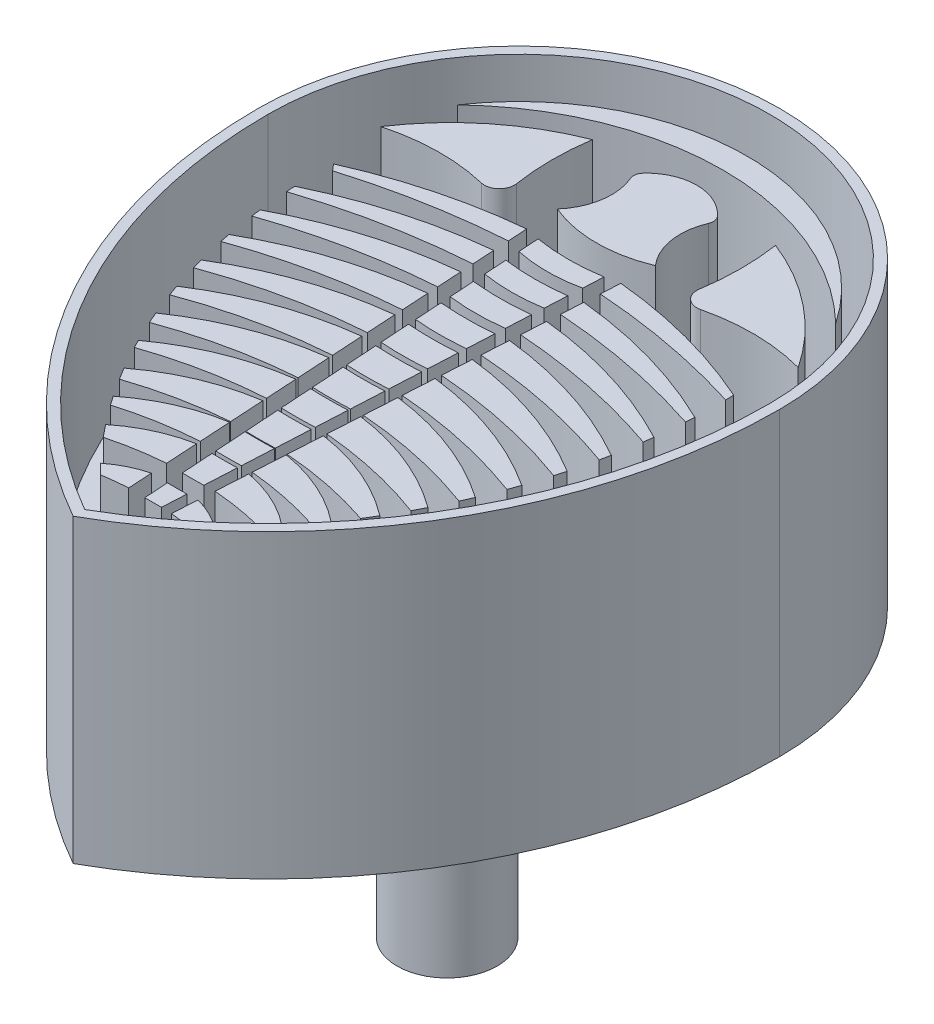
SolidWorks part; units mm, degrees
ref_plane "Přední rovina" through (0, 0, 0) normal (0, 0, 1) x (1, 0, 0)
ref_plane "Horní rovina" through (0, 0, 0) normal (0, 1, 0) x (1, 0, 0)
ref_plane "Pravá rovina" through (0, 0, 0) normal (1, 0, 0) x (0, 0, -1)
sketch "Skica1" plane through (0, 0, 0) normal (0, 1, 0) x (1, 0, 0)
  arc A0 (5, 0) -> (-5, 0) centre (0, 0) ccw
  arc A1 (-5, 0) -> (0, -8.6603) centre (5, 0) ccw
  arc A2 (0, -8.6603) -> (5, 0) centre (-5, 0) ccw
  dimension "D1" = 10
extrude "Přidat vysunutím1" add sketch "Skica1" against normal blind 3
sketch "Skica2" plane through (0, 0, 0) normal (0, 1, 0) x (1, 0, 0)
  line L0 (-0.9396, 1.0946) -> (-0.9163, 0.7054)
  line L1 (0.9396, 1.0946) -> (0.9163, 0.7054)
  line L2 (-0.4639, -6.8657) -> (-0.435, -7.3481)
  line L3 (-0.521, -5.9092) -> (-0.4831, -6.5437)
  line L4 (0.521, -5.9092) -> (0.4831, -6.5437)
  line L5 (-0.5631, -5.2058) -> (-0.5258, -5.8294)
  line L6 (-0.605, -4.5041) -> (-0.5642, -5.1865)
  line L7 (0.605, -4.5041) -> (0.5642, -5.1865)
  line L8 (0.6469, -3.8031) -> (0.6088, -4.4409)
  line L9 (-0.6469, -3.8031) -> (-0.6097, -4.4257)
  line L10 (-0.6887, -3.1028) -> (-0.6498, -3.7549)
  line L11 (0.6887, -3.1028) -> (0.6498, -3.7549)
  line L12 (0.7306, -2.4028) -> (0.6935, -3.0231)
  line L13 (-0.7306, -2.4028) -> (-0.6935, -3.0231)
  line L14 (-0.7724, -1.703) -> (-0.7376, -2.2844)
  line L15 (0.7724, -1.703) -> (0.7376, -2.2844)
  line L16 (0.8142, -1.0034) -> (0.7821, -1.5408)
  line L17 (-0.8142, -1.0034) -> (-0.7821, -1.5408)
  line L18 (-0.856, -0.304) -> (-0.8267, -0.7938)
  line L19 (0.856, -0.304) -> (0.8267, -0.7938)
  line L20 (0.8978, 0.3954) -> (0.8715, -0.0448)
  line L21 (-0.8978, 0.3954) -> (-0.8715, -0.0448)
  line L22 (0.4639, -6.8657) -> (0.434, -7.3648)
  line L23 (0.5631, -5.2058) -> (0.5249, -5.8452)
  line L24 (-0.6539, 1.0367) -> (-0.6272, 0.6279)
  line L25 (0.6621, 1.0381) -> (0.641, 0.6309)
  line L26 (-0.6089, 0.3483) -> (-0.5795, -0.1033)
  line L27 (0.6264, 0.3507) -> (0.6031, -0.0994)
  line L28 (0.5906, -0.3401) -> (0.5649, -0.8356)
  line L29 (-0.5638, -0.3429) -> (-0.5314, -0.8398)
  line L30 (0.5547, -1.0329) -> (0.5266, -1.5735)
  line L31 (-0.5186, -1.0361) -> (-0.4832, -1.5778)
  line L32 (-0.4732, -1.7307) -> (-0.4351, -2.3147)
  line L33 (0.5186, -1.7274) -> (0.4884, -2.3105)
  line L34 (-0.4279, -2.4264) -> (-0.3873, -3.0482)
  line L35 (0.4826, -2.4231) -> (0.4504, -3.0442)
  line L36 (-0.3369, -3.8204) -> (-0.2962, -4.4435)
  line L37 (0.4103, -3.8173) -> (0.378, -4.4401)
  line L38 (0.4464, -3.1197) -> (0.4126, -3.7721)
  line L39 (-0.3824, -3.123) -> (-0.3398, -3.7759)
  line L40 (0.3377, -5.2158) -> (0.3054, -5.8391)
  line L41 (-0.2456, -5.2184) -> (-0.205, -5.8419)
  line L42 (0.374, -4.5159) -> (0.3387, -5.1981)
  line L43 (-0.2913, -4.5188) -> (-0.2468, -5.2012)
  line L44 (-0.1999, -5.9198) -> (-0.1585, -6.554)
  line L45 (0.3013, -5.9174) -> (0.2685, -6.5517)
  line L46 (-0.1376, -6.874) -> (-0.1061, -7.3562)
  line L47 (0.2518, -6.8721) -> (0.2268, -7.3544)
  arc A0 (3.7723, 2.5471) -> (-3.7723, 2.5471) centre (0, 0) ccw
  arc A1 (3.7723, 2.5471) -> (-3.7723, 2.5471) centre (0, -1.3616) ccw
  arc A2 (-1.826, 3.293) -> (-4.1627, 1.4083) centre (0, -1.3616) ccw
  arc A7 (4.1627, 1.4083) -> (2.1882, 1.4375) centre (3.118, -2.4529) ccw
  arc A8 (-1.826, 3.293) -> (-1.8221, 1.7756) centre (3.118, 2.5471) ccw
  arc A9 (4.1627, 1.4083) -> (1.826, 3.293) centre (0, -1.3616) ccw
  arc A10 (1.8221, 1.7756) -> (1.826, 3.293) centre (-3.118, 2.5471) ccw
  arc A11 (-2.1882, 1.4375) -> (-1.8221, 1.7756) centre (-2.1185, 1.7293) ccw
  arc A12 (1.8221, 1.7756) -> (2.1882, 1.4375) centre (2.1185, 1.7293) ccw
  arc A13 (-2.1882, 1.4375) -> (-4.1627, 1.4083) centre (-3.118, -2.4529) ccw
  arc A15 (-0.9784, 1.7445) -> (-0.778, 3.0046) centre (-1.8819, 2.5341) ccw
  arc A16 (0.778, 3.0046) -> (0.9784, 1.7445) centre (1.8819, 2.5341) ccw
  arc A17 (-0.7425, 3.2169) -> (-0.778, 3.0046) centre (-0.594, 3.083) ccw
  arc A18 (0.778, 3.0046) -> (0.7425, 3.2169) centre (0.594, 3.083) ccw
  arc A20 (3.996, 0.288) -> (0.9396, 1.0946) centre (0, -8.6603) ccw
  arc A21 (-0.9784, 1.7445) -> (0.9784, 1.7445) centre (0, 4.0705) ccw
  arc A22 (0.7425, 3.2169) -> (-0.7425, 3.2169) centre (0, 2.5471) ccw
  arc A23 (3.989, -0.4811) -> (0.8978, 0.3954) centre (0, -8.6603) ccw
  arc A24 (3.9271, -1.2348) -> (0.856, -0.304) centre (0, -8.6603) ccw
  arc A25 (3.8134, -1.9708) -> (0.8142, -1.0034) centre (0, -8.6603) ccw
  arc A26 (3.6503, -2.6874) -> (0.7724, -1.703) centre (0, -8.6603) ccw
  arc A27 (3.4403, -3.3825) -> (0.7306, -2.4028) centre (0, -8.6603) ccw
  arc A28 (3.1856, -4.0546) -> (0.6887, -3.1028) centre (0, -8.6603) ccw
  arc A29 (2.8883, -4.702) -> (0.6469, -3.8031) centre (0, -8.6603) ccw
  arc A30 (2.5505, -5.3234) -> (0.605, -4.5041) centre (0, -8.6603) ccw
  arc A31 (2.1739, -5.9172) -> (0.5631, -5.2058) centre (0, -8.6603) ccw
  arc A32 (1.76, -6.4825) -> (0.521, -5.9092) centre (0, -8.6603) ccw
  arc A33 (1.1422, -7.2005) -> (0.4639, -6.8657) centre (0, -8.6603) ccw
  arc A34 (-4.9974, -0.2302) -> (0, -8.6603) centre (5, 0) ccw
  arc A35 (0, -8.6603) -> (4.9974, -0.2302) centre (-5, 0) ccw
  arc A36 (3.9992, 0.1259) -> (0.9163, 0.7054) centre (0, -12.6603) ccw
  arc A37 (3.9794, -0.6572) -> (0.8715, -0.0448) centre (0, -12.6603) ccw
  arc A38 (3.903, -1.4236) -> (0.8267, -0.7938) centre (0, -12.6603) ccw
  arc A39 (3.773, -2.1713) -> (0.7821, -1.5408) centre (0, -12.6603) ccw
  arc A40 (3.5921, -2.8981) -> (0.7376, -2.2844) centre (0, -12.6603) ccw
  arc A41 (3.3628, -3.6022) -> (0.6935, -3.0231) centre (0, -12.6603) ccw
  arc A42 (3.0872, -4.2819) -> (0.6498, -3.7549) centre (0, -12.6603) ccw
  arc A43 (2.7721, -4.9273) -> (0.6088, -4.4409) centre (-0.103, -12.6603) ccw
  arc A44 (2.4059, -5.5618) -> (0.5642, -5.1865) centre (0, -12.6603) ccw
  arc A45 (2.01, -6.1506) -> (0.5249, -5.8452) centre (-0.103, -12.6603) ccw
  arc A46 (1.5622, -6.7269) -> (0.4831, -6.5437) centre (0, -12.6603) ccw
  arc A47 (0.9136, -7.4357) -> (0.434, -7.3648) centre (-0.103, -12.6603) ccw
  arc A51 (0.9136, -7.4357) -> (1.1422, -7.2005) centre (-6.5, 0) ccw
  arc A52 (-0.9396, 1.0946) -> (-3.996, 0.288) centre (0, -8.6603) ccw
  arc A53 (-1.1422, -7.2005) -> (-0.9445, -7.4046) centre (6.5, 0) ccw
  arc A54 (-1.76, -6.4825) -> (-1.5622, -6.7269) centre (6.5, 0) ccw
  arc A55 (-2.1739, -5.9172) -> (-2.0475, -6.0984) centre (6.5, 0) ccw
  arc A56 (-2.5505, -5.3234) -> (-2.4059, -5.5618) centre (6.5, 0) ccw
  arc A57 (-2.8883, -4.702) -> (-2.8049, -4.8651) centre (6.5, 0) ccw
  arc A58 (-3.1856, -4.0546) -> (-3.0872, -4.2819) centre (6.5, 0) ccw
  arc A59 (-3.4403, -3.3825) -> (-3.3628, -3.6022) centre (6.5, 0) ccw
  arc A60 (-3.6503, -2.6874) -> (-3.5921, -2.8981) centre (6.5, 0) ccw
  arc A61 (-3.8134, -1.9708) -> (-3.773, -2.1713) centre (6.5, 0) ccw
  arc A62 (-3.9271, -1.2348) -> (-3.903, -1.4236) centre (6.5, 0) ccw
  arc A63 (-3.989, -0.4811) -> (-3.9794, -0.6572) centre (6.5, 0) ccw
  arc A64 (3.9992, 0.1259) -> (3.996, 0.288) centre (-6.5, 0) ccw
  arc A65 (3.9794, -0.6572) -> (3.989, -0.4811) centre (-6.5, 0) ccw
  arc A66 (3.903, -1.4236) -> (3.9271, -1.2348) centre (-6.5, 0) ccw
  arc A67 (3.773, -2.1713) -> (3.8134, -1.9708) centre (-6.5, 0) ccw
  arc A68 (3.5921, -2.8981) -> (3.6503, -2.6874) centre (-6.5, 0) ccw
  arc A69 (3.3628, -3.6022) -> (3.4403, -3.3825) centre (-6.5, 0) ccw
  arc A70 (3.0872, -4.2819) -> (3.1856, -4.0546) centre (-6.5, 0) ccw
  arc A71 (2.7721, -4.9273) -> (2.8883, -4.702) centre (-6.5, 0) ccw
  arc A72 (2.4059, -5.5618) -> (2.5505, -5.3234) centre (-6.5, 0) ccw
  arc A73 (2.01, -6.1506) -> (2.1739, -5.9172) centre (-6.5, 0) ccw
  arc A74 (1.5622, -6.7269) -> (1.76, -6.4825) centre (-6.5, 0) ccw
  arc A75 (-0.9163, 0.7054) -> (-3.9992, 0.1259) centre (0, -12.6603) ccw
  arc A76 (-0.8978, 0.3954) -> (-3.989, -0.4811) centre (0, -8.6603) ccw
  arc A77 (-0.8715, -0.0448) -> (-3.9794, -0.6572) centre (0, -12.6603) ccw
  arc A78 (-0.856, -0.304) -> (-3.9271, -1.2348) centre (0, -8.6603) ccw
  arc A79 (-0.8267, -0.7938) -> (-3.903, -1.4236) centre (0, -12.6603) ccw
  arc A80 (-0.8142, -1.0034) -> (-3.8134, -1.9708) centre (0, -8.6603) ccw
  arc A81 (-0.7821, -1.5408) -> (-3.773, -2.1713) centre (0, -12.6603) ccw
  arc A82 (-0.7724, -1.703) -> (-3.6503, -2.6874) centre (0, -8.6603) ccw
  arc A83 (-0.7376, -2.2844) -> (-3.5921, -2.8981) centre (0, -12.6603) ccw
  arc A84 (-0.7306, -2.4028) -> (-3.4403, -3.3825) centre (0, -8.6603) ccw
  arc A85 (-0.6935, -3.0231) -> (-3.3628, -3.6022) centre (0, -12.6603) ccw
  arc A86 (-0.6887, -3.1028) -> (-3.1856, -4.0546) centre (0, -8.6603) ccw
  arc A87 (-0.6498, -3.7549) -> (-3.0872, -4.2819) centre (0, -12.6603) ccw
  arc A88 (-0.6469, -3.8031) -> (-2.8883, -4.702) centre (0, -8.6603) ccw
  arc A89 (-0.6097, -4.4257) -> (-2.8049, -4.8651) centre (-0.103, -12.6603) ccw
  arc A90 (-0.605, -4.5041) -> (-2.5505, -5.3234) centre (0, -8.6603) ccw
  arc A91 (-0.5642, -5.1865) -> (-2.4059, -5.5618) centre (0, -12.6603) ccw
  arc A92 (-0.5631, -5.2058) -> (-2.1739, -5.9172) centre (0, -8.6603) ccw
  arc A93 (-0.5258, -5.8294) -> (-2.0475, -6.0984) centre (-0.103, -12.6603) ccw
  arc A94 (-0.521, -5.9092) -> (-1.76, -6.4825) centre (0, -8.6603) ccw
  arc A95 (-0.4831, -6.5437) -> (-1.5622, -6.7269) centre (0, -12.6603) ccw
  arc A96 (-0.4639, -6.8657) -> (-1.1422, -7.2005) centre (0, -8.6603) ccw
  arc A97 (-0.435, -7.3481) -> (-0.9445, -7.4046) centre (-0.103, -12.6603) ccw
  arc A98 (-3.996, 0.288) -> (-3.9992, 0.1259) centre (6.5, 0) ccw
  arc A100 (5, 0) -> (-5, 0) centre (0, 0) ccw construction
  arc A108 (-0.2913, -4.5188) -> (0.374, -4.5159) centre (0, 5) ccw
  arc A111 (-0.1376, -6.874) -> (0.2518, -6.8721) centre (0, 5) ccw
  arc A112 (-0.6539, 1.0367) -> (0.6621, 1.0381) centre (0, 5) ccw
  arc A113 (-0.5186, -1.0361) -> (0.5547, -1.0329) centre (0, 5) ccw
  arc A114 (-0.4732, -1.7307) -> (0.5186, -1.7274) centre (0, 5) ccw
  arc A115 (-0.5795, -0.1033) -> (0.6031, -0.0994) centre (0, 3.5471) ccw
  arc A116 (-0.6089, 0.3483) -> (0.6264, 0.3507) centre (0, 5) ccw
  arc A117 (-0.5638, -0.3429) -> (0.5906, -0.3401) centre (0, 5) ccw
  arc A118 (-0.4279, -2.4264) -> (0.4826, -2.4231) centre (0, 5) ccw
  arc A119 (-0.4351, -2.3147) -> (0.4884, -2.3105) centre (0, 3.5471) ccw
  arc A120 (-0.3873, -3.0482) -> (0.4504, -3.0442) centre (0, 3.5471) ccw
  arc A121 (-0.3824, -3.123) -> (0.4464, -3.1197) centre (0, 5) ccw
  arc A122 (-0.3369, -3.8204) -> (0.4103, -3.8173) centre (0, 5) ccw
  arc A123 (-0.1999, -5.9198) -> (0.3013, -5.9174) centre (0, 5) ccw
  arc A124 (-0.2456, -5.2184) -> (0.3377, -5.2158) centre (0, 5) ccw
  arc A125 (-0.1585, -6.554) -> (0.2685, -6.5517) centre (0, 3.5471) ccw
  arc A129 (-3.9876, 0.2918) -> (-3.8789, 0.163) centre (0, 3.5471) ccw
  arc A134 (-0.2468, -5.2012) -> (0.3387, -5.1981) centre (0, 3.5471) ccw
  arc A138 (-0.6272, 0.6279) -> (0.641, 0.6309) centre (0, 3.5471) ccw
  arc A139 (-0.4832, -1.5778) -> (0.5266, -1.5735) centre (0, 3.5471) ccw
  arc A140 (-0.2962, -4.4435) -> (0.378, -4.4401) centre (0, 3.5471) ccw
  arc A141 (-0.5314, -0.8398) -> (0.5649, -0.8356) centre (0, 3.5471) ccw
  arc A142 (-0.3398, -3.7759) -> (0.4126, -3.7721) centre (0, 3.5471) ccw
  arc A143 (-0.205, -5.8419) -> (0.3054, -5.8391) centre (0, 3.5471) ccw
  arc A144 (-0.1061, -7.3562) -> (0.2268, -7.3544) centre (0, 3.5471) ccw
  point P44 (0, -12.6603)
  dimension "D1" = 4
  dimension "D4" = 1.5
  dimension "D5" = 1.5
extrude "Přidat vysunutím2" add sketch "Skica2" along normal blind 2.5 contours A97 L2 A96 A53 | A95 L3 A94 A54 | A93 L5 A92 A55 | A91 L6 A90 A56 | A89 L9 A88 A57 | A87 L10 A86 A58 | A85 L13 A84 A59 | A83 L14 A82 A60 | A81 L17 A80 A61 | A77 L21 A76 A63 | A52 A129 A75 L0 | A13 A11 A8 A2 | A1 A0 | A18 A22 A17 A15 A21 A16 | A10 A12 A7 A9 | L24 A138 L25 A112 | A116 L26 A115 L27 | L29 A141 L28 A117 | L31 A139 L30 A113 | L32 A119 L33 A114 | L34 A120 L35 A118 | L39 A142 L38 A121 | L36 A140 L37 A122 | L43 A134 L42 A108 | L41 A143 L40 A124 | L44 A125 L45 A123 | L46 A144 L47 A111 | A47 A51 A33 L22 | A46 A74 A32 L4 | A45 A73 A31 L23 | A44 A72 A30 L7 | A43 A71 A29 L8 | A42 A70 A28 L11 | A41 A69 A27 L12 | A40 A68 A26 L15 | A39 A67 A25 L16 | A38 A66 A24 L19 | A37 A65 A23 L20 | A84 A59 A85 L13 | A78 A62 A79 L18 | A36 L1 A20 A64 region at (-2.2521, 0, -0.6787) region at (-0.7289, 0, 7.169) region at (-1.0328, 0, 6.351) region at (1.0328, 0, 6.351) region at (-1.2291, 0, 5.6712) region at (-1.4297, 0, 5.0378) region at (1.4297, 0, 5.0378) region at (1.6079, 0, 4.3464) region at (-1.5774, 0, 4.3173) region at (-1.7578, 0, 3.6642) region at (1.7578, 0, 3.6642) region at (1.8946, 0, 2.9605) region at (-1.8946, 0, 2.9605) region at (-2.0121, 0, 2.2477) region at (2.0121, 0, 2.2477) region at (2.1095, 0, 1.527) region at (-2.1095, 0, 1.527) region at (2.1859, 0, 0.7993) region at (2.2402, 0, 0.0656) region at (-2.2402, 0, 0.0656) region at (0.728, 0, 7.1802) region at (1.2436, 0, 5.6936) region at (0.0053, 0, -0.7937) region at (0.0101, 0, -0.0961) region at (0.0149, 0, 0.6092) region at (0.0198, 0, 1.3186) region at (0.0246, 0, 2.0295) region at (0.0294, 0, 2.7402) region at (0.0387, 0, 4.13) region at (0.0341, 0, 3.4492) region at (0.0481, 0, 5.5244) region at (0.0436, 0, 4.8548) region at (0.0528, 0, 6.229) region at (0.0587, 0, 7.1089) region at (0, 0, -4.1486) region at (-2.6742, 0, -2.1513) region at (2.6742, 0, -2.1513) region at (0, 0, -2.4956)
extrude "Vysunout tenkostěnný1" add sketch "Skica1<2>" along normal mid plane 6 separate body thin thin type one direction wall 0.2
sketch "Skica1<2>" plane through (0, 0, 0) normal (0, 1, 0) x (1, 0, 0) same geometry as "Skica1"
ref_plane "Rovina1" through (0, -3, 0) normal (0, -1, 0) x (-1, 0, 0)
sketch "Skica4" plane through (0, -3, 0) normal (0, -1, 0) x (-1, 0, 0)
  circle A0 centre (0, -1.4317) radius 1
  dimension "D1" = 2
extrude "Přidat vysunutím3" add sketch "Skica4" along normal blind 5
ref_plane "Rovina2" through (0, -8, 0) normal (0, -1, 0) x (-1, 0, 0)
sketch "Skica5" plane through (0, -8, 0) normal (0, -1, 0) x (-1, 0, 0)
  circle A0 centre (0, -1.4317) radius 3
  dimension "D1" = 6
scale "Měřítko2" scale about origin uniform scaling yes scale factor 10
